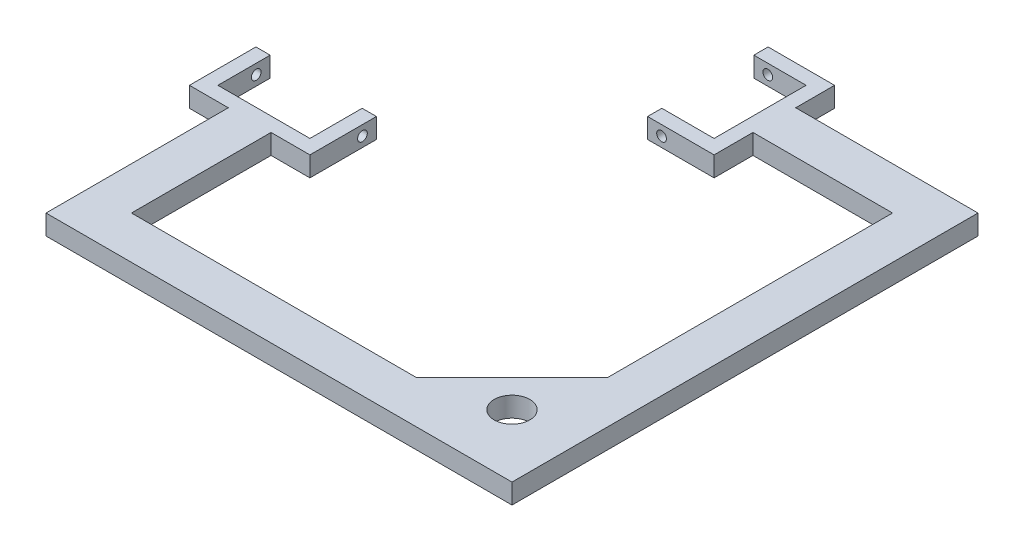
SolidWorks part; units mm, degrees
ref_plane "Front Plane" through (0, 0, 0) normal (0, 0, 1) x (1, 0, 0)
ref_plane "Top Plane" through (0, 0, 0) normal (0, 1, 0) x (1, 0, 0)
ref_plane "Right Plane" through (0, 0, 0) normal (1, 0, 0) x (0, 0, -1)
sketch "Sketch1" plane through (0, 0, 0) normal (0, 1, 0) x (1, 0, 0)
  line L0 (-84.9, -24.6552) -> (-84.9, -42.9952)
  line L1 (-84.9, -42.9952) -> (-52.6, -42.9952)
  line L2 (-52.6, -42.9952) -> (-52.6, -24.6552)
  line L3 (-52.6, -24.6552) -> (-47.6, -24.6552)
  line L4 (-47.6, -24.6552) -> (-47.6, -47.9952)
  line L5 (-47.6, -47.9952) -> (-61.25, -47.9952)
  line L6 (-84.9, -24.6552) -> (-89.9, -24.6552)
  line L7 (-89.9, -24.6552) -> (-89.9, -47.9952)
  line L8 (-89.9, -47.9952) -> (-76.25, -47.9952)
  line L9 (-76.25, -47.9952) -> (-76.25, -111.9952)
  line L10 (-61.25, -47.9952) -> (-61.25, -96.9952)
  line L11 (-76.25, -111.9952) -> (38.75, -111.9952)
  line L12 (-61.25, -96.9952) -> (38.75, -96.9952)
  line L14 (23.34, 36.5948) -> (23.34, 22.9448)
  line L15 (23.34, 22.9448) -> (0, 22.9448)
  line L16 (0, 22.9448) -> (0, 27.9448)
  line L17 (0, 27.9448) -> (18.34, 27.9448)
  line L18 (18.34, 27.9448) -> (18.34, 60.2448)
  line L19 (18.34, 60.2448) -> (0, 60.2448)
  line L20 (0, 60.2448) -> (0, 65.2448)
  line L21 (0, 65.2448) -> (23.34, 65.2448)
  line L22 (23.34, 65.2448) -> (23.34, 51.5948)
  line L28 (23.34, 36.5948) -> (72.34, 36.5948)
  line L29 (72.34, 36.5948) -> (72.34, -63.4052)
  line L30 (23.34, 51.5948) -> (87.34, 51.5948)
  line L31 (87.34, 51.5948) -> (87.34, -63.4052)
  line L32 (72.34, -63.4052) -> (38.75, -96.9952)
  line L33 (38.75, -111.9952) -> (87.34, -111.9952)
  line L34 (87.34, -111.9952) -> (87.34, -63.4052)
  circle A2 centre (65.34, -89.9952) radius 6.25
  dimension "D11" = 7
  dimension "D12" = 7
  dimension "D13" = 12.5
  dimension "D1" = 5
  dimension "D2" = 18.34
  dimension "D3" = 5
  dimension "D4" = 32.3
  dimension "D5" = 100
  dimension "D6" = 15
  dimension "D7" = 49
  dimension "D8" = 15
  dimension "D9" = 70.94
  dimension "D10" = 70.94
extrude "Boss-Extrude1" add sketch "Sketch1" along normal blind 7
sketch "Sketch2" plane through (0, 0, -22.9448) normal (0, 0, 1) x (1, 0, 0)
  line L0 (0, 7) -> (0, 0) construction
  line L1 (0, 7) -> (23.34, 7) construction
  line L3 (0, 0) -> (23.34, 0) construction
  circle A0 centre (4.9, 3.5) radius 1.7
  dimension "D1" = 3.4
  dimension "D2" = 4.9
  dimension "D3" = 3.5
  dimension "D4" = 3.5
extrude "Cut-Extrude1" cut sketch "Sketch2" against normal blind 50
sketch "Sketch3" plane through (-47.6, 0, 0) normal (1, 0, 0) x (0, 0, -1)
  line L0 (-24.6552, 7) -> (-24.6552, 0) construction
  line L1 (-47.9952, 7) -> (-24.6552, 7) construction
  line L2 (-47.9952, 0) -> (-24.6552, 0) construction
  circle A0 centre (-29.5552, 3.5) radius 1.7
  dimension "D1" = 3.4
  dimension "D3" = 3.5
  dimension "D4" = 3.5
  dimension "D2" = 4.9
extrude "Cut-Extrude2" cut sketch "Sketch3" against normal blind 50
